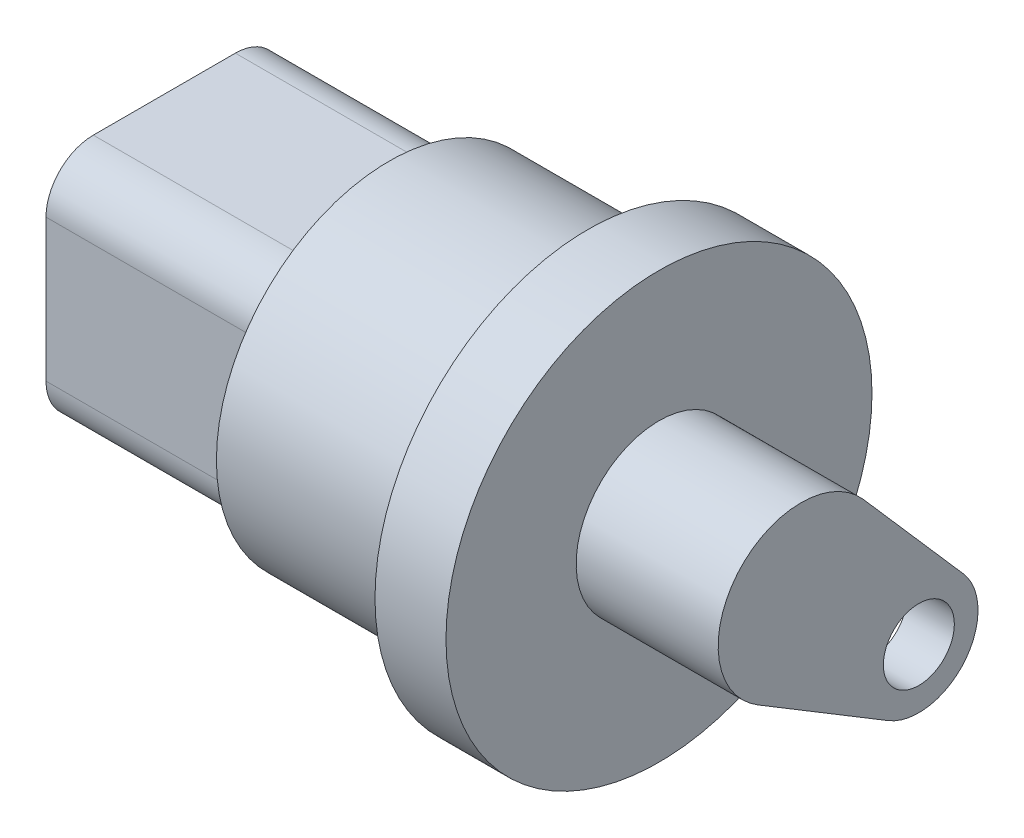
SolidWorks part; units mm, degrees
ref_plane "Front Plane" through (0, 0, 0) normal (0, 0, 1) x (1, 0, 0)
ref_plane "Top Plane" through (0, 0, 0) normal (0, 1, 0) x (1, 0, 0)
ref_plane "Right Plane" through (0, 0, 0) normal (1, 0, 0) x (0, 0, -1)
sketch "Sketch2" plane through (0, 0, 0) normal (1, 0, 0) x (0, 0, -1)
  line L1 (-5, 5) -> (5, 5)
  line L2 (-5, 5) -> (-5, -5)
  line L3 (-5, -5) -> (5, -5)
  line L4 (5, 5) -> (5, -5)
  line L5 (-5, 5) -> (5, -5) construction
  line L6 (-5, -5) -> (5, 5) construction
  circle A0 centre (0, 0) radius 7.3
  circle A1 centre (0, 0) radius 9
  dimension "D1" = 14.6
  dimension "D4" = 18
  dimension "D2" = 10
  dimension "D3" = 10
extrude "Boss-Extrude1" add sketch "Sketch2" along normal blind 3 contours A1
extrude "Boss-Extrude2" add sketch "Sketch2<4>" against normal blind 8.4 contours A0
sketch "Sketch2<4>" plane through (0, 0, 0) normal (1, 0, 0) x (0, 0, -1) same geometry as "Sketch2"
extrude "Boss-Extrude3" add sketch "Sketch2<6>" against normal blind 9.5 from surface contours L4 L3 L2 L1 starting at face at (-8.4, 0, -7.3)
sketch "Sketch2<6>" plane through (0, 0, 0) normal (1, 0, 0) x (0, 0, -1) same geometry as "Sketch2"
sketch "Sketch6" plane through (0, 0, 0) normal (1, 0, 0) x (0, 0, -1)
  line L0 (-5, -5) -> (5, 5) construction
  line L1 (0, 0) -> (8.6111, -7.2256) construction
  line L2 (2.6355, 2.3031) -> (6.8618, -2.533)
  line L4 (-1.8105, -2.9954) -> (3.6861, -6.3177)
  line L5 (0, 0) -> (0, -13.1884) construction
  circle A0 centre (4.9793, -4.1781) radius 2.5
  circle A1 centre (0, 0) radius 9
  circle A2 centre (0, 0) radius 9 construction
  circle A3 centre (0, 0) radius 3.5
  circle A4 centre (4.9793, -4.1781) radius 1.5
  point P12 (0, 0)
  dimension "D2" = 5
  dimension "D3" = 7
  dimension "D4" = 3
  dimension "D1" = 50
extrude "Boss-Extrude6" add sketch "Sketch6" along normal blind 4 from surface contours A3 starting at face at (3, 0, -9)
extrude "Boss-Extrude7" add sketch "Sketch6<4>" along normal blind 2 from surface contours A3 L4 A0 L2 | A3 | A0 A4 region at (0, -2.4234, -2.8881) region at (0, 0, 0) region at (0, -3.3244, -7.2536) starting at face at (7, 0, -3.5)
sketch "Sketch6<4>" plane through (0, 0, 0) normal (1, 0, 0) x (0, 0, -1) same geometry as "Sketch6"
extrude "Cut-Extrude1" cut sketch "Sketch6<5>" against normal up to surface from surface contours A4 L1 | L1 A4 region at (0, -4.1781, -4.9793) up to face at (0, 0, -7.3) starting at face at (3, 0, -3.5)
sketch "Sketch6<5>" plane through (0, 0, 0) normal (1, 0, 0) x (0, 0, -1) same geometry as "Sketch6"
fillet "Fillet1" radius 2 4 edges at (-13.15, 5, 5) (-13.15, -5, 5) (-13.15, -5, -5) (-13.15, 5, -5)
